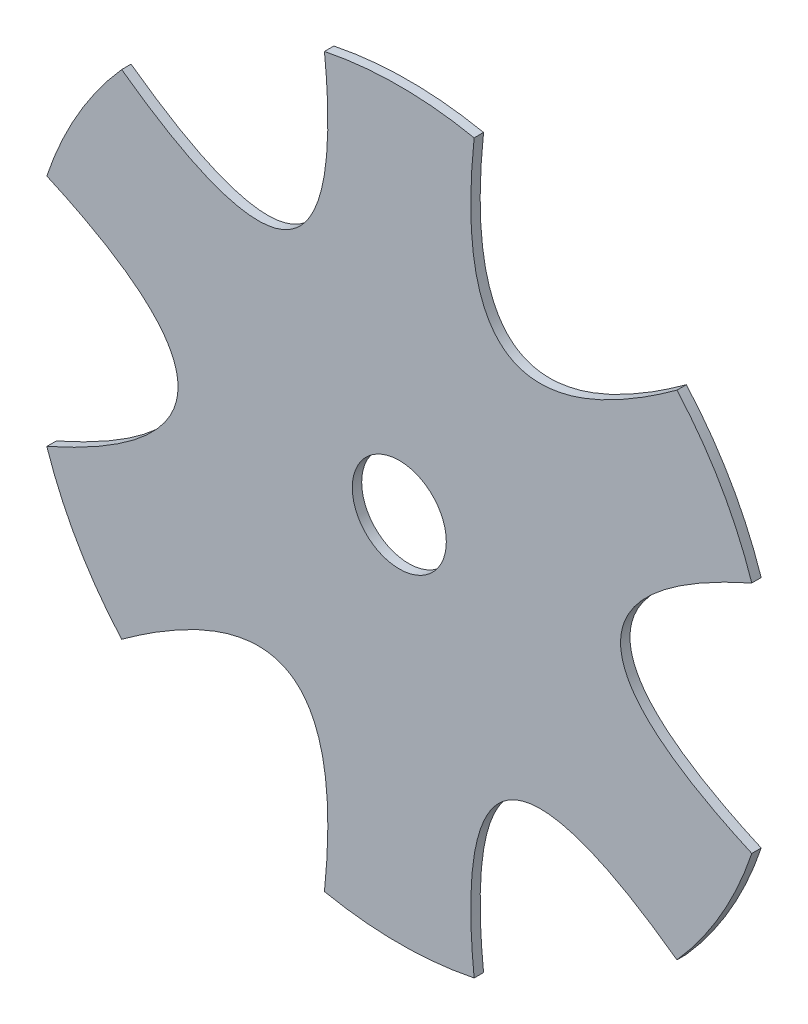
SolidWorks part; units mm, degrees
ref_plane "Front Plane" through (0, 0, 0) normal (0, 0, 1) x (1, 0, 0)
ref_plane "Top Plane" through (0, 0, 0) normal (0, 1, 0) x (1, 0, 0)
ref_plane "Right Plane" through (0, 0, 0) normal (1, 0, 0) x (0, 0, -1)
sketch "Sketch1" plane through (0, 0, 0) normal (0, 0, 1) x (1, 0, 0)
  circle A0 centre (0, 0) radius 125.4125
  dimension "D1" = 250.825
extrude "Boss-Extrude1" add sketch "Sketch1" along normal blind 3.175
sketch "Sketch2" plane through (0, 0, 3.175) normal (0, 0, 1) x (1, 0, 0)
  arc A0 (93.7481, 83.3041) -> (25.2694, 122.8403) centre (0, 0) ccw
  spline S0 degree 2 poles (93.7481, 83.3041) (15.2066, 26.3386) (25.2694, 122.8403) knots 0 0 0 1 1 1
extrude "Cut-Extrude1" cut sketch "Sketch2" against normal through all
pattern_circular "CirPattern1" count 6 over 360 about axis through (0, 0, 3.175) along (0, 0, -1) of "Cut-Extrude1" reverse direction yes
sketch "Sketch3" plane through (0, 0, 0) normal (0, 0, -1) x (-1, 0, 0)
  circle A0 centre (0, 0) radius 15.875
  dimension "D1" = 31.75
extrude "Cut-Extrude2" cut sketch "Sketch3" against normal blind 50.8 contours A0
